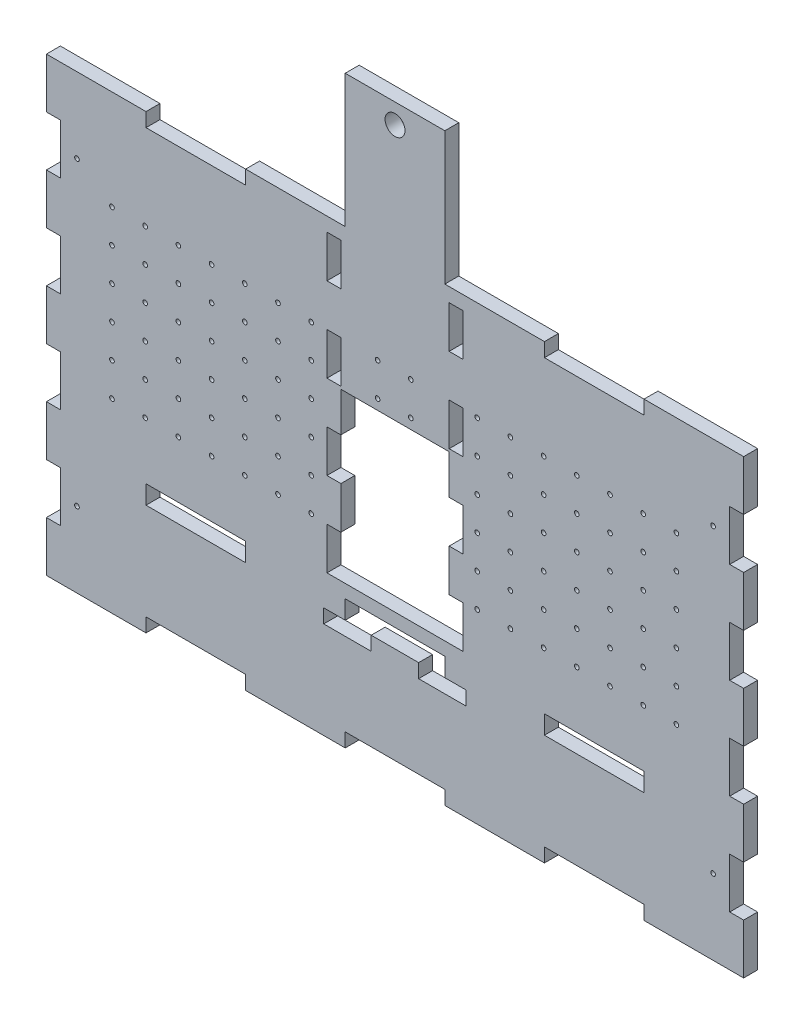
SolidWorks part; units mm, degrees
ref_plane "Front Plane" through (0, 0, 0) normal (0, 0, 1) x (1, 0, 0)
ref_plane "Top Plane" through (0, 0, 0) normal (0, 1, 0) x (1, 0, 0)
ref_plane "Right Plane" through (0, 0, 0) normal (1, 0, 0) x (0, 0, -1)
sketch "Sketch1" plane through (0, 0, 0) normal (0, 0, 1) x (1, 0, 0)
  line L1 (-127.8759, 88.4641) -> (138.8241, 88.4641)
  line L2 (-127.8759, 88.4641) -> (-127.8759, -84.2559)
  line L3 (-127.8759, -84.2559) -> (138.8241, -84.2559)
  line L4 (138.8241, 88.4641) -> (138.8241, -84.2559)
  dimension "D1" = 266.7
  dimension "D2" = 172.72
extrude "Boss-Extrude1" add sketch "Sketch1" along normal blind 5.334
sketch "Sketch2" plane through (0, 0, 5.334) normal (0, 0, 1) x (1, 0, 0)
  line L0 (-127.8759, -84.2559) -> (138.8241, -84.2559) construction
  line L1 (-89.7759, -84.2559) -> (-51.6759, -84.2559)
  line L2 (-89.7759, -84.2559) -> (-89.7759, -78.9219)
  line L3 (-89.7759, -78.9219) -> (-51.6759, -78.9219)
  line L4 (-51.6759, -84.2559) -> (-51.6759, -78.9219)
  line L5 (-89.7759, -78.9219) -> (-127.8759, -78.9219) construction
  line L6 (-13.5759, -84.2559) -> (24.5241, -84.2559)
  line L7 (-13.5759, -84.2559) -> (-13.5759, -78.9219)
  line L8 (-13.5759, -78.9219) -> (24.5241, -78.9219)
  line L9 (24.5241, -84.2559) -> (24.5241, -78.9219)
  line L10 (62.6241, -84.2559) -> (100.7241, -84.2559)
  line L11 (62.6241, -84.2559) -> (62.6241, -78.9219)
  line L12 (62.6241, -78.9219) -> (100.7241, -78.9219)
  line L13 (100.7241, -84.2559) -> (100.7241, -78.9219)
  line L14 (-127.8759, 88.4641) -> (-127.8759, -84.2559) construction
  line L15 (-51.6759, -78.9219) -> (-13.5759, -78.9219) construction
  line L16 (24.5241, -78.9219) -> (62.6241, -78.9219) construction
  line L17 (62.6241, -78.9219) -> (62.364, -79.7896) construction
  line L18 (100.7241, -78.9219) -> (138.8241, -78.9219) construction
  line L19 (138.8241, -84.2559) -> (138.8241, 88.4641) construction
  line L20 (-127.8759, 2.1041) -> (138.8241, 2.1041) construction
  line L21 (100.7241, 88.4641) -> (100.7241, 83.1301)
  line L22 (62.6241, 83.1301) -> (100.7241, 83.1301)
  line L23 (62.6241, 88.4641) -> (62.6241, 83.1301)
  line L24 (24.5241, 88.4641) -> (24.5241, 83.1301)
  line L25 (-13.5759, 83.1301) -> (24.5241, 83.1301)
  line L26 (-13.5759, 88.4641) -> (-13.5759, 83.1301)
  line L27 (-51.6759, 88.4641) -> (-51.6759, 83.1301)
  line L28 (-89.7759, 83.1301) -> (-51.6759, 83.1301)
  line L29 (-89.7759, 88.4641) -> (-89.7759, 83.1301)
  line L30 (62.6241, 88.4641) -> (100.7241, 88.4641)
  line L31 (-13.5759, 88.4641) -> (24.5241, 88.4641)
  line L32 (-89.7759, 88.4641) -> (-51.6759, 88.4641)
  dimension "D1" = 5.334
extrude "Cut-Extrude1" cut sketch "Sketch2" against normal through all
sketch "Sketch5" plane through (0, 0, 5.334) normal (0, 0, 1) x (1, 0, 0)
  line L0 (-51.6759, -34.8224) -> (-13.5759, -34.8224) construction
  line L1 (-89.7759, -34.8224) -> (-51.6759, -34.8224)
  line L2 (-89.7759, -34.8224) -> (-89.7759, -41.9344)
  line L3 (-89.7759, -41.9344) -> (-51.6759, -41.9344)
  line L4 (-51.6759, -34.8224) -> (-51.6759, -41.9344)
  line L5 (-13.5759, -34.8224) -> (24.5241, -34.8224)
  line L6 (-13.5759, -34.8224) -> (-13.5759, -41.9344)
  line L7 (-13.5759, -41.9344) -> (24.5241, -41.9344)
  line L8 (24.5241, -34.8224) -> (24.5241, -41.9344)
  line L9 (62.6241, -34.8224) -> (100.7241, -34.8224)
  line L10 (62.6241, -34.8224) -> (62.6241, -41.9344)
  line L11 (62.6241, -41.9344) -> (100.7241, -41.9344)
  line L12 (100.7241, -34.8224) -> (100.7241, -41.9344)
  line L13 (-51.6759, -41.9344) -> (-13.5759, -41.9344) construction
  line L14 (24.5241, -34.8224) -> (62.6241, -34.8224) construction
  line L15 (24.5241, -41.9344) -> (62.6241, -41.9344) construction
  line L16 (-89.7759, -34.8224) -> (-127.8759, -34.8224) construction
  line L17 (-127.8759, 88.4641) -> (-127.8759, -84.2559) construction
  line L18 (-89.7759, -41.9344) -> (-127.8759, -41.9344) construction
  line L19 (100.7241, -34.8224) -> (138.8241, -34.8224) construction
  line L20 (138.8241, -84.2559) -> (138.8241, 88.4641) construction
  line L21 (100.7241, -41.9344) -> (138.8241, -41.9344) construction
  dimension "D1" = 7.112
extrude "Cut-Extrude3" cut sketch "Sketch5" against normal through all
sketch "Sketch8" plane through (0, 0, 5.334) normal (0, 0, 1) x (1, 0, 0)
  line L0 (-13.5759, -41.9344) -> (24.5241, -41.9344) construction
  line L1 (-21.7977, -47.2684) -> (-3.6478, -47.2684)
  line L2 (-21.7977, -47.2684) -> (-21.7977, -41.9344)
  line L3 (-21.7977, -41.9344) -> (-3.6478, -41.9344)
  line L4 (-3.6478, -47.2684) -> (-3.6478, -41.9344)
  line L5 (-3.6478, -47.2684) -> (14.5022, -47.2684) construction
  line L6 (14.5022, -41.9344) -> (32.6521, -41.9344)
  line L7 (14.5022, -41.9344) -> (14.5022, -47.2684)
  line L8 (14.5022, -47.2684) -> (32.6521, -47.2684)
  line L9 (32.6521, -41.9344) -> (32.6521, -47.2684)
  line L10 (14.5022, -47.2684) -> (14.3218, -49.4005) construction
  line L11 (14.5022, -41.9344) -> (-3.6478, -41.9344) construction
  line L12 (62.6241, -34.8224) -> (62.6241, -41.9344) construction
  line L13 (-51.6759, -41.9344) -> (-51.6759, -34.8224) construction
  dimension "D1" = 5.334
  dimension "D2" = 29.972
  dimension "D3" = 29.8782
extrude "Cut-Extrude6" cut sketch "Sketch8" against normal through all
sketch "Sketch9" plane through (0, 0, 5.334) normal (0, 0, 1) x (1, 0, 0)
  line L0 (-127.8759, 88.4641) -> (-127.8759, -84.2559) construction
  line L1 (-127.8759, -65.0647) -> (-122.5419, -65.0647)
  line L2 (-127.8759, -65.0647) -> (-127.8759, -45.8736)
  line L3 (-127.8759, -45.8736) -> (-122.5419, -45.8736)
  line L4 (-122.5419, -65.0647) -> (-122.5419, -45.8736)
  line L5 (-122.5419, 69.273) -> (-122.5419, 88.4641) construction
  line L6 (-127.8759, -26.6825) -> (-122.5419, -26.6825)
  line L7 (-127.8759, -26.6825) -> (-127.8759, -7.4914)
  line L8 (-127.8759, -7.4914) -> (-122.5419, -7.4914)
  line L9 (-122.5419, -26.6825) -> (-122.5419, -7.4914)
  line L10 (-127.8759, 11.6997) -> (-122.5419, 11.6997)
  line L11 (-127.8759, 11.6997) -> (-127.8759, 30.8908)
  line L12 (-127.8759, 30.8908) -> (-122.5419, 30.8908)
  line L13 (-122.5419, 11.6997) -> (-122.5419, 30.8908)
  line L14 (-127.8759, 50.0819) -> (-122.5419, 50.0819)
  line L15 (-127.8759, 50.0819) -> (-127.8759, 69.273)
  line L16 (-127.8759, 69.273) -> (-122.5419, 69.273)
  line L17 (-122.5419, 50.0819) -> (-122.5419, 69.273)
  line L18 (-89.7759, 88.4641) -> (-127.8759, 88.4641) construction
  line L19 (-122.5419, 50.0819) -> (-122.5419, 30.8908) construction
  line L20 (-122.5419, 11.6997) -> (-122.5419, -7.4914) construction
  line L21 (-122.5419, -26.6825) -> (-122.5419, -45.8736) construction
  line L22 (-122.5419, -65.0647) -> (-122.5419, -84.2559) construction
  line L23 (-127.8759, -84.2559) -> (-89.7759, -84.2559) construction
  line L24 (5.4741, 83.1301) -> (5.4741, -78.9219) construction
  line L25 (-13.5759, 83.1301) -> (24.5241, 83.1301) construction
  line L26 (24.5241, -78.9219) -> (-13.5759, -78.9219) construction
  line L27 (133.4901, -65.0647) -> (133.4901, -84.2559) construction
  line L28 (133.4901, -26.6825) -> (133.4901, -45.8736) construction
  line L29 (133.4901, 11.6997) -> (133.4901, -7.4914) construction
  line L30 (133.4901, 50.0819) -> (133.4901, 30.8908) construction
  line L31 (133.4901, 69.273) -> (133.4901, 88.4641) construction
  line L32 (133.4901, 50.0819) -> (133.4901, 69.273)
  line L33 (138.8241, 69.273) -> (133.4901, 69.273)
  line L34 (138.8241, 50.0819) -> (138.8241, 69.273)
  line L35 (138.8241, 50.0819) -> (133.4901, 50.0819)
  line L36 (133.4901, 11.6997) -> (133.4901, 30.8908)
  line L37 (138.8241, 30.8908) -> (133.4901, 30.8908)
  line L38 (138.8241, 11.6997) -> (138.8241, 30.8908)
  line L39 (138.8241, 11.6997) -> (133.4901, 11.6997)
  line L40 (133.4901, -26.6825) -> (133.4901, -7.4914)
  line L41 (138.8241, -7.4914) -> (133.4901, -7.4914)
  line L42 (138.8241, -26.6825) -> (138.8241, -7.4914)
  line L43 (138.8241, -26.6825) -> (133.4901, -26.6825)
  line L44 (133.4901, -65.0647) -> (133.4901, -45.8736)
  line L45 (138.8241, -45.8736) -> (133.4901, -45.8736)
  line L46 (138.8241, -65.0647) -> (138.8241, -45.8736)
  line L47 (138.8241, -65.0647) -> (133.4901, -65.0647)
  dimension "D1" = 5.334
extrude "Cut-Extrude7" cut sketch "Sketch9" against normal through all
sketch "Sketch10" plane through (0, 88.4641, 0) normal (0, 1, 0) x (1, 0, 0)
  line L1 (24.5241, -5.334) -> (62.6241, -5.334)
  line L2 (24.5241, -5.334) -> (24.5241, 0)
  line L3 (24.5241, 0) -> (62.6241, 0)
  line L4 (62.6241, -5.334) -> (62.6241, 0)
extrude "Boss-Extrude2" add sketch "Sketch10" along normal blind 50.8
sketch "Sketch11" plane through (0, 0, 0) normal (0, 0, -1) x (-1, 0, 0)
  line L0 (-24.5241, 83.1301) -> (-24.5241, 139.2641) construction
  line L1 (-24.5241, 88.4641) -> (-31.1281, 88.4641)
  line L2 (-24.5241, 88.4641) -> (-24.5241, 129.1041)
  line L3 (-24.5241, 129.1041) -> (-31.1281, 129.1041)
  line L4 (-31.1281, 88.4641) -> (-31.1281, 129.1041)
  line L5 (13.5759, 88.4641) -> (51.6759, 88.4641) construction
  dimension "D1" = 6.604
  dimension "D2" = 40.64
  dimension "D3" = 0
extrude "Cut-Extrude8" cut sketch "Sketch11" against normal through all
sketch "Sketch12" plane through (0, 0, 5.334) normal (0, 0, 1) x (1, 0, 0)
  line L0 (62.6241, 139.2641) -> (62.6241, 83.1301) construction
  circle A0 centre (43.5741, 130.4765) radius 3.81
  dimension "D1" = 19.05
extrude "Cut-Extrude9" cut sketch "Sketch12" against normal through all
sketch "Sketch14" plane through (0, 0, 5.334) normal (0, 0, 1) x (1, 0, 0)
  line L0 (-89.7759, 88.4641) -> (-127.8759, 88.4641) construction
  circle A0 centre (-102.7976, 50.3641) radius 0.889
  circle A1 centre (-90.0976, 50.3641) radius 0.889
  circle A2 centre (-77.3976, 50.3641) radius 0.889
  circle A3 centre (-64.6976, 50.3641) radius 0.889
  circle A4 centre (-51.9976, 50.3641) radius 0.889
  circle A5 centre (-39.2976, 50.3641) radius 0.889
  circle A6 centre (-26.5976, 50.3641) radius 0.889
  circle A8 centre (-1.1976, 50.3641) radius 0.889
  circle A9 centre (11.5024, 50.3641) radius 0.889
  circle A11 centre (36.9024, 50.3641) radius 0.889
  circle A12 centre (49.6024, 50.3641) radius 0.889
  circle A13 centre (62.3024, 50.3641) radius 0.889
  circle A14 centre (75.0024, 50.3641) radius 0.889
  circle A15 centre (87.7024, 50.3641) radius 0.889
  circle A16 centre (100.4024, 50.3641) radius 0.889
  circle A17 centre (113.1024, 50.3641) radius 0.889
  circle A18 centre (-102.7976, 37.6641) radius 0.889
  circle A19 centre (-90.0976, 37.6641) radius 0.889
  circle A20 centre (-77.3976, 37.6641) radius 0.889
  circle A21 centre (-64.6976, 37.6641) radius 0.889
  circle A22 centre (-51.9976, 37.6641) radius 0.889
  circle A23 centre (-39.2976, 37.6641) radius 0.889
  circle A24 centre (-26.5976, 37.6641) radius 0.889
  circle A26 centre (-1.1976, 37.6641) radius 0.889
  circle A27 centre (11.5024, 37.6641) radius 0.889
  circle A29 centre (36.9024, 37.6641) radius 0.889
  circle A30 centre (49.6024, 37.6641) radius 0.889
  circle A31 centre (62.3024, 37.6641) radius 0.889
  circle A32 centre (75.0024, 37.6641) radius 0.889
  circle A33 centre (87.7024, 37.6641) radius 0.889
  circle A34 centre (100.4024, 37.6641) radius 0.889
  circle A35 centre (113.1024, 37.6641) radius 0.889
  circle A36 centre (-102.7976, 24.9641) radius 0.889
  circle A37 centre (-90.0976, 24.9641) radius 0.889
  circle A38 centre (-77.3976, 24.9641) radius 0.889
  circle A39 centre (-64.6976, 24.9641) radius 0.889
  circle A40 centre (-51.9976, 24.9641) radius 0.889
  circle A41 centre (-39.2976, 24.9641) radius 0.889
  circle A42 centre (-26.5976, 24.9641) radius 0.889
  circle A44 centre (-1.1976, 24.9641) radius 0.889
  circle A45 centre (11.5024, 24.9641) radius 0.889
  circle A47 centre (36.9024, 24.9641) radius 0.889
  circle A48 centre (49.6024, 24.9641) radius 0.889
  circle A49 centre (62.3024, 24.9641) radius 0.889
  circle A50 centre (75.0024, 24.9641) radius 0.889
  circle A51 centre (87.7024, 24.9641) radius 0.889
  circle A52 centre (100.4024, 24.9641) radius 0.889
  circle A53 centre (113.1024, 24.9641) radius 0.889
  circle A54 centre (-102.7976, 12.2641) radius 0.889
  circle A55 centre (-90.0976, 12.2641) radius 0.889
  circle A56 centre (-77.3976, 12.2641) radius 0.889
  circle A57 centre (-64.6976, 12.2641) radius 0.889
  circle A58 centre (-51.9976, 12.2641) radius 0.889
  circle A59 centre (-39.2976, 12.2641) radius 0.889
  circle A60 centre (-26.5976, 12.2641) radius 0.889
  circle A65 centre (36.9024, 12.2641) radius 0.889
  circle A66 centre (49.6024, 12.2641) radius 0.889
  circle A67 centre (62.3024, 12.2641) radius 0.889
  circle A68 centre (75.0024, 12.2641) radius 0.889
  circle A69 centre (87.7024, 12.2641) radius 0.889
  circle A70 centre (100.4024, 12.2641) radius 0.889
  circle A71 centre (113.1024, 12.2641) radius 0.889
  circle A72 centre (-102.7976, -0.4359) radius 0.889
  circle A73 centre (-90.0976, -0.4359) radius 0.889
  circle A74 centre (-77.3976, -0.4359) radius 0.889
  circle A75 centre (-64.6976, -0.4359) radius 0.889
  circle A76 centre (-51.9976, -0.4359) radius 0.889
  circle A77 centre (-39.2976, -0.4359) radius 0.889
  circle A78 centre (-26.5976, -0.4359) radius 0.889
  circle A79 centre (-13.8976, -0.4359) radius 0.889
  circle A80 centre (-1.1976, -0.4359) radius 0.889
  circle A81 centre (11.5024, -0.4359) radius 0.889
  circle A82 centre (24.2024, -0.4359) radius 0.889
  circle A83 centre (36.9024, -0.4359) radius 0.889
  circle A84 centre (49.6024, -0.4359) radius 0.889
  circle A85 centre (62.3024, -0.4359) radius 0.889
  circle A86 centre (75.0024, -0.4359) radius 0.889
  circle A87 centre (87.7024, -0.4359) radius 0.889
  circle A88 centre (100.4024, -0.4359) radius 0.889
  circle A89 centre (113.1024, -0.4359) radius 0.889
  circle A90 centre (-102.7976, -13.1359) radius 0.889
  circle A91 centre (-90.0976, -13.1359) radius 0.889
  circle A92 centre (-77.3976, -13.1359) radius 0.889
  circle A93 centre (-64.6976, -13.1359) radius 0.889
  circle A94 centre (-51.9976, -13.1359) radius 0.889
  circle A95 centre (-39.2976, -13.1359) radius 0.889
  circle A96 centre (-26.5976, -13.1359) radius 0.889
  circle A97 centre (-13.8976, -13.1359) radius 0.889
  circle A98 centre (-1.1976, -13.1359) radius 0.889
  circle A99 centre (11.5024, -13.1359) radius 0.889
  circle A100 centre (24.2024, -13.1359) radius 0.889
  circle A101 centre (36.9024, -13.1359) radius 0.889
  circle A102 centre (49.6024, -13.1359) radius 0.889
  circle A103 centre (62.3024, -13.1359) radius 0.889
  circle A104 centre (75.0024, -13.1359) radius 0.889
  circle A105 centre (87.7024, -13.1359) radius 0.889
  circle A106 centre (100.4024, -13.1359) radius 0.889
  circle A107 centre (113.1024, -13.1359) radius 0.889
  circle A108 centre (-1.1976, 12.2641) radius 0.889 [skipped]
  circle A110 centre (11.5024, 12.2641) radius 0.889 [skipped]
  circle A116 centre (24.2024, 50.3641) radius 0.889 [skipped]
  circle A117 centre (-13.8976, 50.3641) radius 0.889 [skipped]
  dimension "D1" = 18
  dimension "D2" = 38.1
  dimension "D4" = 1.778
  dimension "D3" = 6
extrude "Cut-Extrude11" cut sketch "Sketch14" against normal through all
sketch "Sketch15" plane through (0, 0, 5.334) normal (0, 0, 1) x (1, 0, 0)
  line L1 (31.1281, 129.1041) -> (24.5241, 129.1041)
  line L2 (31.1281, 129.1041) -> (31.1281, 139.2641)
  line L3 (31.1281, 139.2641) -> (24.5241, 139.2641)
  line L4 (24.5241, 129.1041) -> (24.5241, 139.2641)
extrude "Cut-Extrude12" cut sketch "Sketch15" against normal through all
sketch "Sketch16" plane through (0, 0, 5.334) normal (0, 0, 1) x (1, 0, 0)
  line L0 (5.4741, 83.1301) -> (5.4741, -78.9219) construction
  line L1 (-15.2269, 33.7576) -> (26.1751, 33.7576)
  line L2 (-15.2269, 33.7576) -> (-15.2269, -29.7424)
  line L3 (-15.2269, -29.7424) -> (26.1751, -29.7424)
  line L4 (26.1751, 33.7576) -> (26.1751, -29.7424)
  line L5 (-13.5759, 83.1301) -> (24.5241, 83.1301) construction
  line L6 (24.5241, -78.9219) -> (-13.5759, -78.9219) construction
  line L7 (24.5241, -34.8224) -> (-13.5759, -34.8224) construction
  dimension "D1" = 63.5
  dimension "D2" = 41.402
  dimension "D3" = 20.701
  dimension "D4" = 5.08
extrude "Cut-Extrude13" cut sketch "Sketch16" against normal through all
sketch "Sketch17" plane through (0, 0, 5.334) normal (0, 0, 1) x (1, 0, 0)
  line L0 (-15.2269, 33.7576) -> (-15.2269, -29.7424) construction
  line L1 (-15.2269, -29.7424) -> (-20.5609, -29.7424)
  line L2 (-15.2269, -29.7424) -> (-15.2269, -13.6178)
  line L3 (-15.2269, -13.6178) -> (-20.5609, -13.6178)
  line L4 (-20.5609, -29.7424) -> (-20.5609, -13.6178)
  line L5 (-15.2269, 2.5069) -> (-20.5609, 2.5069)
  line L6 (-15.2269, 2.5069) -> (-15.2269, 18.6315)
  line L7 (-15.2269, 18.6315) -> (-20.5609, 18.6315)
  line L8 (-20.5609, 2.5069) -> (-20.5609, 18.6315)
  line L9 (-20.5609, -13.6178) -> (-20.5609, 2.5069) construction
  line L10 (-20.5609, 50.8808) -> (-15.2269, 50.8808)
  line L11 (-20.5609, 50.8808) -> (-20.5609, 34.7562)
  line L12 (-20.5609, 34.7562) -> (-15.2269, 34.7562)
  line L13 (-15.2269, 50.8808) -> (-15.2269, 34.7562)
  line L14 (-20.5609, 67.0055) -> (-15.2269, 67.0055)
  line L15 (-20.5609, 67.0055) -> (-20.5609, 83.1301)
  line L16 (-20.5609, 83.1301) -> (-15.2269, 83.1301)
  line L17 (-15.2269, 67.0055) -> (-15.2269, 83.1301)
  line L18 (-20.5609, 18.6315) -> (-20.5609, 34.7562) construction
  line L19 (-20.5609, 67.0055) -> (-20.5609, 50.8808) construction
  line L20 (5.4741, 83.1301) -> (5.4741, -78.9219) construction
  line L21 (-13.5759, 83.1301) -> (24.5241, 83.1301) construction
  line L22 (24.5241, -78.9219) -> (-13.5759, -78.9219) construction
  line L23 (31.5091, 67.0055) -> (31.5091, 50.8808) construction
  line L24 (31.5091, 18.6315) -> (31.5091, 34.7562) construction
  line L25 (31.5091, -13.6178) -> (31.5091, 2.5069) construction
  line L26 (26.1751, 67.0055) -> (26.1751, 83.1301)
  line L27 (31.5091, 83.1301) -> (26.1751, 83.1301)
  line L28 (31.5091, 67.0055) -> (31.5091, 83.1301)
  line L29 (31.5091, 67.0055) -> (26.1751, 67.0055)
  line L30 (26.1751, 50.8808) -> (26.1751, 34.7562)
  line L31 (31.5091, 34.7562) -> (26.1751, 34.7562)
  line L32 (31.5091, 50.8808) -> (31.5091, 34.7562)
  line L33 (31.5091, 50.8808) -> (26.1751, 50.8808)
  line L34 (31.5091, 2.5069) -> (31.5091, 18.6315)
  line L35 (26.1751, 18.6315) -> (31.5091, 18.6315)
  line L36 (26.1751, 2.5069) -> (26.1751, 18.6315)
  line L37 (26.1751, 2.5069) -> (31.5091, 2.5069)
  line L38 (31.5091, -29.7424) -> (31.5091, -13.6178)
  line L39 (26.1751, -13.6178) -> (31.5091, -13.6178)
  line L40 (26.1751, -29.7424) -> (26.1751, -13.6178)
  line L41 (26.1751, -29.7424) -> (31.5091, -29.7424)
  dimension "D1" = 0
  dimension "D2" = 5.334
  dimension "D3" = 5.334
  dimension "D4" = 5.334
extrude "Cut-Extrude14" cut sketch "Sketch17" against normal through all
sketch "Sketch18" plane through (0, 0, 5.334) normal (0, 0, 1) x (1, 0, 0)
  line L0 (24.5241, 83.1301) -> (24.5241, 148.9274) construction
  line L1 (31.1281, 139.2641) -> (62.6241, 139.2641) construction
  line L2 (-13.5759, 83.1301) -> (24.5241, 83.1301)
  line L3 (-13.5759, 83.1301) -> (-13.5759, 139.2641)
  line L4 (-13.5759, 139.2641) -> (24.5241, 139.2641)
  line L5 (24.5241, 83.1301) -> (24.5241, 139.2641)
  dimension "D1" = 0
extrude "Boss-Extrude3" add sketch "Sketch18" against normal blind 5.334
sketch "Sketch19" plane through (0, 0, 5.334) normal (0, 0, 1) x (1, 0, 0)
  line L1 (31.1281, 88.4641) -> (65.8849, 88.4641)
  line L2 (31.1281, 88.4641) -> (31.1281, 143.4078)
  line L3 (31.1281, 143.4078) -> (65.8849, 143.4078)
  line L4 (65.8849, 88.4641) -> (65.8849, 143.4078)
extrude "Cut-Extrude15" cut sketch "Sketch19" against normal through all
sketch "Sketch20" plane through (0, 0, 5.334) normal (0, 0, 1) x (1, 0, 0)
  line L0 (5.4741, 139.2641) -> (5.4741, 29.9476) construction
  line L1 (24.5241, 139.2641) -> (-13.5759, 139.2641) construction
  circle A0 centre (5.4741, 131.6441) radius 3.81
  dimension "D1" = 7.62
  dimension "D3" = 7.62
  dimension "D2" = 0
extrude "Cut-Extrude16" cut sketch "Sketch20" against normal through all contours A0
sketch "Sketch21" plane through (0, 0, 5.334) normal (0, 0, 1) x (1, 0, 0)
  line L0 (133.4901, 59.6775) -> (-122.5419, 59.6775) construction
  line L1 (133.4901, 69.273) -> (133.4901, 50.0819) construction
  line L2 (-122.5419, 50.0819) -> (-122.5419, 69.273) construction
  line L3 (-122.5419, -55.4692) -> (133.4901, -55.4692) construction
  line L4 (-122.5419, -65.0647) -> (-122.5419, -45.8736) construction
  line L5 (133.4901, -45.8736) -> (133.4901, -65.0647) construction
  line L6 (138.8241, 2.1041) -> (-127.8759, 2.1041) construction
  line L7 (138.8241, -7.4914) -> (138.8241, 11.6997) construction
  line L8 (-127.8759, 11.6997) -> (-127.8759, -7.4914) construction
  line L9 (5.4741, 139.2641) -> (5.4741, -78.9219) construction
  line L10 (24.5241, 139.2641) -> (-13.5759, 139.2641) construction
  line L11 (24.5241, -78.9219) -> (-13.5759, -78.9219) construction
  circle A0 centre (127.1401, 59.6775) radius 0.889
  circle A1 centre (-116.1919, 59.6775) radius 0.889
  circle A2 centre (-116.1919, -55.4692) radius 0.889
  circle A3 centre (127.1401, -55.4692) radius 0.889
  dimension "D1" = 1.778
  dimension "D2" = 0
  dimension "D3" = 6.35
extrude "Cut-Extrude17" cut sketch "Sketch21" against normal through all
equation "\"MDF\"= .21in"
equation "\"Foamcore\"= .13in"
equation "\"Gmaterial\"= \"MDF\""
equation "\"D1@Boss-Extrude1\"=\"MDF\""
equation "\"D1@Sketch2\"=\"MDF\""
equation "\"D1@Sketch5\"=\"MDF\"+0.07"
equation "\"D1@Sketch8\"=\"MDF\""
equation "\"D1@Sketch9\"=\"MDF\""
equation "\"D1@Sketch11\"=\"MDF\"+.05"
equation "\"D2@Sketch17\"=\"MDF\""
equation "\"D3@Sketch17\"=\"MDF\""
equation "\"D4@Sketch17\"=\"MDF\""
equation "\"D1@Boss-Extrude3\"=\"MDF\""
